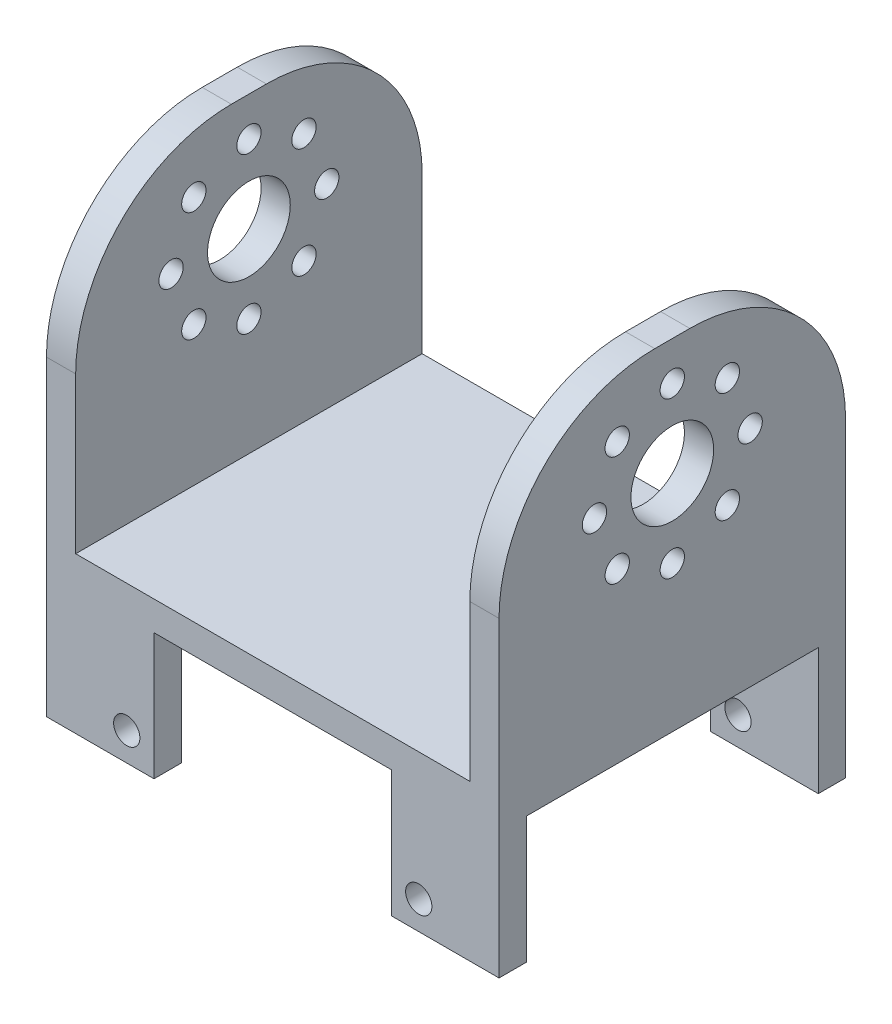
SolidWorks part; units mm, degrees
ref_plane "Front Plane" through (0, 0, 0) normal (0, 0, 1) x (1, 0, 0)
ref_plane "Top Plane" through (0, 0, 0) normal (0, 1, 0) x (1, 0, 0)
ref_plane "Right Plane" through (0, 0, 0) normal (1, 0, 0) x (0, 0, -1)
sketch "Sketch1" plane through (0, 0, 0) normal (0, 1, 0) x (1, 0, 0)
  line L1 (-23.25, -17.8) -> (23.25, -17.8)
  line L2 (-23.25, -17.8) -> (-23.25, 17.8)
  line L3 (-23.25, 17.8) -> (23.25, 17.8)
  line L4 (23.25, -17.8) -> (23.25, 17.8)
  line L5 (-23.25, -17.8) -> (23.25, 17.8) construction
  line L6 (-23.25, 17.8) -> (23.25, -17.8) construction
  point P0 (0, 0)
  dimension "D1" = 46.5
  dimension "D2" = 35.6
extrude "Boss-Extrude1" add sketch "Sketch1" along normal blind 2
sketch "Sketch2" plane through (0, 2, 0) normal (0, 1, 0) x (1, 0, 0)
  line L0 (-23.25, -17.8) -> (23.25, -17.8) construction
  line L1 (-23.25, 17.8) -> (-20.25, 17.8)
  line L2 (-23.25, 17.8) -> (-23.25, -17.8)
  line L3 (-23.25, -17.8) -> (-20.25, -17.8)
  line L4 (-20.25, 17.8) -> (-20.25, -17.8)
  line L6 (23.25, 17.8) -> (20.25, 17.8)
  line L7 (23.25, 17.8) -> (23.25, -17.8)
  line L8 (23.25, -17.8) -> (20.25, -17.8)
  line L9 (20.25, 17.8) -> (20.25, -17.8)
  dimension "D1" = 3
  dimension "D2" = 3
extrude "Boss-Extrude2" add sketch "Sketch2" along normal blind 50
sketch "Sketch3" plane through (23.25, 0, 0) normal (1, 0, 0) x (0, 0, -1)
  line L0 (-17.8, 52) -> (17.8, 52) construction
  circle A0 centre (0, 40) radius 4.25
  dimension "D1" = 8.5
  dimension "D2" = 12
extrude "Cut-Extrude1" cut sketch "Sketch3" against normal through all
sketch "Sketch5" plane through (23.25, 0, 0) normal (1, 0, 0) x (0, 0, -1)
  circle A0 centre (0, 40) radius 8
  dimension "D1" = 16
sketch "Sketch6" plane through (23.25, 0, 0) normal (1, 0, 0) x (0, 0, -1)
  circle A0 centre (0, 32) radius 1.25
  circle A1 centre (0, 40) radius 8 construction
  circle A2 centre (-5.6569, 34.3431) radius 1.25
  circle A3 centre (-8, 40) radius 1.25
  circle A4 centre (-5.6569, 45.6569) radius 1.25
  circle A5 centre (0, 48) radius 1.25
  circle A6 centre (5.6569, 45.6569) radius 1.25
  circle A7 centre (8, 40) radius 1.25
  circle A8 centre (5.6569, 34.3431) radius 1.25
  point P21 (0, 40)
  dimension "D1" = 2.5
  dimension "D3" = 8
  dimension "D2" = 8
extrude "Cut-Extrude3" cut sketch "Sketch6" against normal through all
fillet "Fillet5" radius 16 4 edges at (-21.75, 52, 17.8) (21.75, 52, 17.8) (21.75, 52, -17.8) (-21.75, 52, -17.8)
extrude "Cut-Extrude6" cut sketch "Sketch1<2>" along normal blind 20
sketch "Sketch1<2>" plane through (0, 0, 0) normal (0, 1, 0) x (1, 0, 0) same geometry as "Sketch1"
sketch "Sketch8" plane through (0, 20, 0) normal (0, -1, 0) x (1, 0, 0)
  line L1 (-23.25, 17.8) -> (23.25, 17.8)
  line L2 (-23.25, 17.8) -> (-23.25, -17.8)
  line L3 (-23.25, -17.8) -> (23.25, -17.8)
  line L4 (23.25, 17.8) -> (23.25, -17.8)
extrude "Boss-Extrude3" add sketch "Sketch8" along normal blind 3
sketch "Sketch9" plane through (23.25, 0, 0) normal (1, 0, 0) x (0, 0, -1)
  line L1 (-17.8, 17) -> (17.8, 17)
  line L2 (-17.8, 17) -> (-17.8, 4)
  line L3 (-17.8, 4) -> (17.8, 4)
  line L4 (17.8, 17) -> (17.8, 4)
  dimension "D1" = 13
  dimension "D2" = 35.6
extrude "Boss-Extrude4" add sketch "Sketch9" against normal up to surface (46.5 mm away) up to face at (-23.25, 40, -4.25)
sketch "Sketch12" plane through (0, 0, -17.8) normal (0, 0, -1) x (-1, 0, 0)
  line L0 (23.25, 4) -> (-23.25, 4) construction
  line L1 (-12.2, 4) -> (12.2, 4)
  line L2 (-12.2, 4) -> (-12.2, 17)
  line L3 (-12.2, 17) -> (12.2, 17)
  line L4 (12.2, 4) -> (12.2, 17)
  line L5 (20.25, 20) -> (-20.25, 20) construction
  line L6 (23.25, 36) -> (23.25, 4) construction
  dimension "D1" = 3
  dimension "D2" = 24.4
  dimension "D3" = 11.05
extrude "Cut-Extrude9" cut sketch "Sketch12" against normal through all
sketch "Sketch13" plane through (12.2, 0, 0) normal (-1, 0, 0) x (0, 0, 1)
  line L0 (-17.8, 4) -> (17.8, 4) construction
  line L1 (-15, 4) -> (15, 4)
  line L2 (-15, 4) -> (-15, 17)
  line L3 (-15, 17) -> (15, 17)
  line L4 (15, 4) -> (15, 17)
  line L5 (17.8, 36) -> (17.8, 4) construction
  dimension "D1" = 13
  dimension "D2" = 2.8
  dimension "D3" = 30
extrude "Cut-Extrude10" cut sketch "Sketch13" along normal through all and the other way through all
sketch "Sketch15" plane through (0, 0, -17.8) normal (0, 0, -1) x (-1, 0, 0)
  line L0 (12.2, 17) -> (-12.2, 17) construction
  line L2 (0, 19.58) -> (0, -19.58) construction
  line L3 (-12.2, 17) -> (-12.2, 4) construction
  circle A0 centre (-15, 6.9) radius 1.35
  circle A1 centre (15, 6.9) radius 1.35
  dimension "D1" = 2.7
  dimension "D2" = 10.1
  dimension "D3" = 2.8
extrude "Cut-Extrude12" cut sketch "Sketch15" against normal through all
